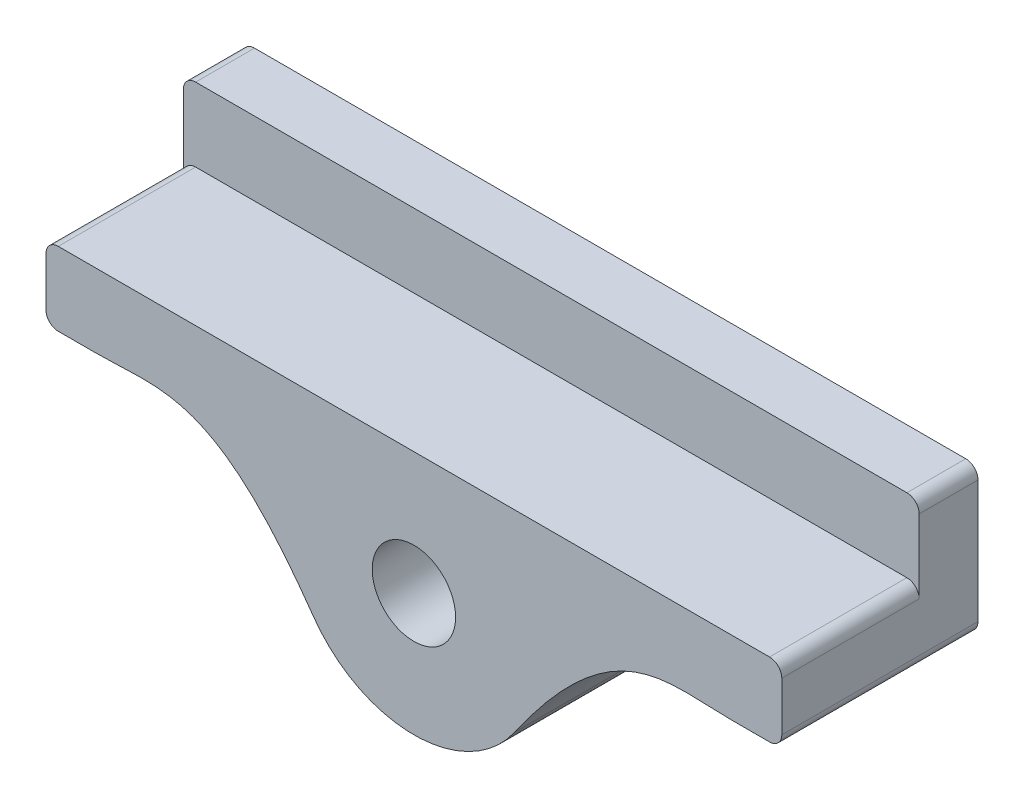
SolidWorks part; units mm, degrees
ref_plane "Front Plane" through (0, 0, 0) normal (0, 0, 1) x (1, 0, 0)
ref_plane "Top Plane" through (0, 0, 0) normal (0, 1, 0) x (1, 0, 0)
ref_plane "Right Plane" through (0, 0, 0) normal (1, 0, 0) x (0, 0, -1)
sketch "Sketch1" plane through (0, 0, 0) normal (0, 0, 1) x (1, 0, 0)
  line L1 (20, 6) -> (20, 0)
  line L2 (20, 0) -> (0, 0) construction
  line L3 (0, 0) -> (5, -2) construction
  line L4 (5, -2) -> (10, 0) construction
  line L6 (18, 0) -> (20, 0)
  line L7 (20, 6) -> (-10, 6)
  line L8 (-10, 6) -> (-10, 0)
  line L9 (5, 13.1237) -> (5, -15.8216) construction
  line L10 (-8, 0) -> (-10, 0)
  line L11 (-10, 0) -> (0, 0) construction
  circle A0 centre (5, -2) radius 1.7
  circle A1 centre (5, -2) radius 5 construction
  arc A2 (0.9013, -4.8637) -> (9.0987, -4.8637) centre (5, -2) ccw
  spline S0 degree 3 poles (18, 0) (15.2603, 0) (13.1314, 0.908) (9.0987, -4.8637) knots 0 0 0 0 1 1 1 1
  spline S1 degree 3 poles (-8, 0) (-5.2603, 0) (-3.1314, 0.908) (0.9013, -4.8637) knots 0 0 0 0 1 1 1 1
  dimension "D4" = 3.4
  dimension "D5" = 2
  dimension "D1" = 30
  dimension "D6" = 10
  dimension "D2" = 6
  dimension "D3" = 2
extrude "Boss-Extrude1" add sketch "Sketch1" along normal blind 8
sketch "Sketch2" plane through (0, 0, 8) normal (0, 0, 1) x (1, 0, 0)
  line L0 (20, 6) -> (-10, 6) construction
  line L1 (-10, 3) -> (20, 3)
  line L2 (-10, 3) -> (-10, 6)
  line L3 (-10, 6) -> (20, 6)
  line L4 (20, 3) -> (20, 6)
  line L5 (-10, 3) -> (20, 6) construction
  line L6 (-10, 6) -> (20, 3) construction
  line L7 (20, 0) -> (20, 6) construction
  circle A1 centre (5, -2) radius 2 construction
  point P0 (5, 4.5)
  dimension "D1" = 3
extrude "Cut-Extrude1" cut sketch "Sketch2" against normal blind 5.6
fillet "Fillet1" radius 0.5 6 edges at (-10, 0, 4) (20, 0, 4) (20, 6, 1.2) (20, 3, 5.2) (-10, 3, 5.2) (-10, 6, 1.2)
sketch "Sketch5" plane through (0, 0, 0) normal (0, 0, -1) x (-1, 0, 0)
  circle A0 centre (-5, -2) radius 3.7
  dimension "D1" = 7.4
extrude "Cut-Extrude2" cut sketch "Sketch5" against normal blind 1
chamfer "Chamfer1" distance 2 angle 45 1 edges at (3.3, -2, 1)
ref_plane "Plane1" through (0, 0, 3) normal (0, 0, 1) x (1, 0, 0)
sketch "Sketch6" plane through (0, 0, 3) normal (0, 0, 1) x (1, 0, 0)
  circle A0 centre (5, -2) radius 1.7 construction
  circle A1 centre (5, -2) radius 1.7
extrude "Boss-Extrude2" add sketch "Sketch6" along normal blind 0.4
ref_plane "Plane2" through (0, 0, 1) normal (0, 0, 1) x (1, 0, 0)
sketch "Sketch7" plane through (0, 0, 1) normal (0, 0, 1) x (1, 0, 0)
  circle A0 centre (5, -2) radius 3.7 construction
  circle A1 centre (5, -2) radius 3.7
extrude "Boss-Extrude3" add sketch "Sketch7" against normal blind 0.4
